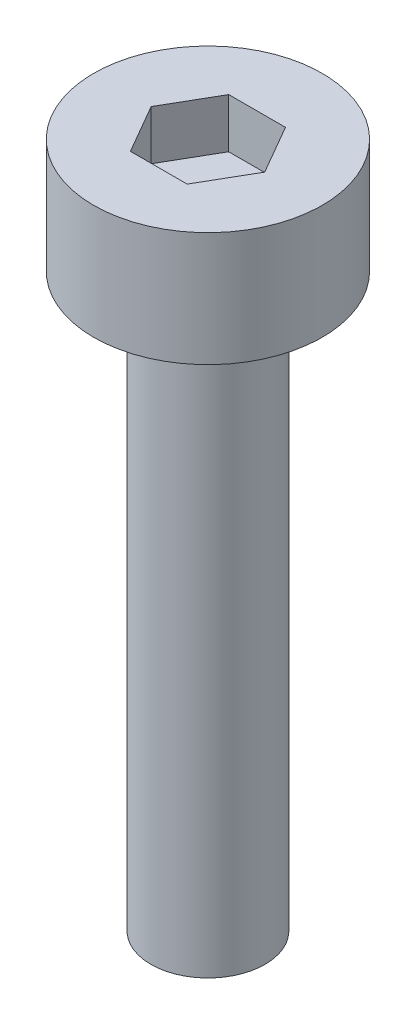
SolidWorks part; units mm, degrees
ref_plane "Front Plane" through (0, 0, 0) normal (0, 0, 1) x (1, 0, 0)
ref_plane "Top Plane" through (0, 0, 0) normal (0, 1, 0) x (1, 0, 0)
ref_plane "Right Plane" through (0, 0, 0) normal (1, 0, 0) x (0, 0, -1)
sketch "Sketch1" plane through (0, 0, 0) normal (0, 1, 0) x (1, 0, 0)
  circle A0 centre (0, 0) radius 1.5
  dimension "D1" = 3
extrude "ScrewShaft" add sketch "Sketch1" along normal blind 15
sketch "Sketch2" plane through (0, 15, 0) normal (0, 1, 0) x (1, 0, 0)
  circle A0 centre (0, 0) radius 3
  dimension "D1" = 6
extrude "Boss-Extrude2" add sketch "Sketch2" along normal blind 3
sketch "Sketch3" plane through (0, 18, 0) normal (0, 1, 0) x (1, 0, 0)
  line L0 (0, 0) -> (0, 1.29) construction
  line L1 (1.4896, 0) -> (0.7448, 1.29)
  line L2 (0.7448, 1.29) -> (-0.7448, 1.29)
  line L3 (-0.7448, 1.29) -> (-1.4896, 0)
  line L4 (-1.4896, 0) -> (-0.7448, -1.29)
  line L5 (-0.7448, -1.29) -> (0.7448, -1.29)
  line L6 (0.7448, -1.29) -> (1.4896, 0)
  circle A0 centre (0, 0) radius 1.29 construction
  dimension "D1" = 2.58
extrude "Cut-Extrude1" cut sketch "Sketch3" against normal blind 1.3
equation "\"X-ROD-SPACING\"=45"
equation "\"Y-ROD-SPACING\"=75"
equation "\"Z-ROD-SPACING\"=17.5"
equation "\"Y-BED-OFFSET\"=2"
equation "\"Y-BED-ROD-INSET\"=3.5"
equation "\"T-SLOT-NUT-FILLET-RADIUS\"=0.5"
equation "\"T-SLOT-SCREW-SHAFT-RADIUS\"=1.55"
equation "\"T-SLOT-SCREW-SHAFT-CUTOUT-LENGTH\"=11"
equation "\"T-SLOT-NUT-DEPTH\"=3.5"
equation "\"T-SLOT-NUT-WIDTH\"=2.85"
equation "\"T-SLOT-NUT-END-DISTANCE\"=8"
equation "\"ACRYLIC-THICKNESS\"=10"
equation "\"ACRYLIC-THICKNESS2\"=4.5"
equation "\"ACRYLIC-TAB-CUTOUT-SIZE\"=\"ACRYLIC-THICKNESS\"+\"ACRYLIC-TAB-TOLERANCE\"*2"
equation "\"ACRYLIC-TAB-WIDTH\"=\"ACRYLIC-THICKNESS\""
equation "\"ACRYLIC-M3-HOLE\"=2.9"
equation "\"SMOOTHROD-CAP-SCREW-DISTANCE\"=20"
equation "\"FRAME-WIDTH-INNER\"=370"
equation "\"NEMA17-HOLE-SPACING\"=31"
equation "\"NEMA17-CENTRAL-CUTOUT\"=22.5"
equation "\"Z-BRACKET-REACH\"=57"
equation "\"TOP-BRACKET-SPACING\"=40"
equation "\"SMOOTHROD-X-LENGTH\"=350"
equation "\"SMOOTHROD-Y-LENGTH\"=350"
equation "\"SMOOTHROD-Z-LENGTH\"=350"
equation "\"SMOOTHROD-TIGHTENING-HEADROOM\"=.25"
equation "\"LEADSCREW-Z-LENGTH\"=300"
equation "\"SCREW-LENGTH-FRAME\"=\"ACRYLIC-THICKNESS\" + 10"
equation "\"SCREW-HEAD-RADIUS\"=6"
equation "\"PRINTED-X-SMOOTHROD-DIAMETER\"=8.8"
equation "\"PRINTED-X-SMOOTHROD-CUTOUT\"=10"
equation "\"PRINTED-X-BASE-HEIGHT\"=10"
equation "\"PRINTED-LM8UU-CUTOUT-SIZE\"=15.5"
equation "\"PRINTED-LM8UU-CUTOUT-LENGTH\"=24.5"
equation "\"PRINTED-X-IDLER-HEIGHT\"=16"
equation "\"PSU-MOUNTING-WIDTH\"=95"
equation "\"PSU-MOUNTING-HEIGHT\"=177"
equation "\"D1@ScrewShaft\"=\"SCREW-LENGTH-MOTOR\""
equation "\"D1@Sketch2\"=\"SCREW-HEAD-RADIUS\""
equation "\"Y-BED-SCREW-SPACING\"=209"
equation "\"Y-BED-SCREW-CUTOUT-SLOT-HEIGHT\"=2.5"
equation "\"Z-ROD-INSET\"=13.5"
equation "\"SCREW-LENGTH-MOTOR\"=\"ACRYLIC-THICKNESS\" + 5"
equation "\"Y-BELT-TO-ROD-DISTANCE\"=20"
equation "\"SPOOL-HOLDER-ROD-SPACING\"=150"
